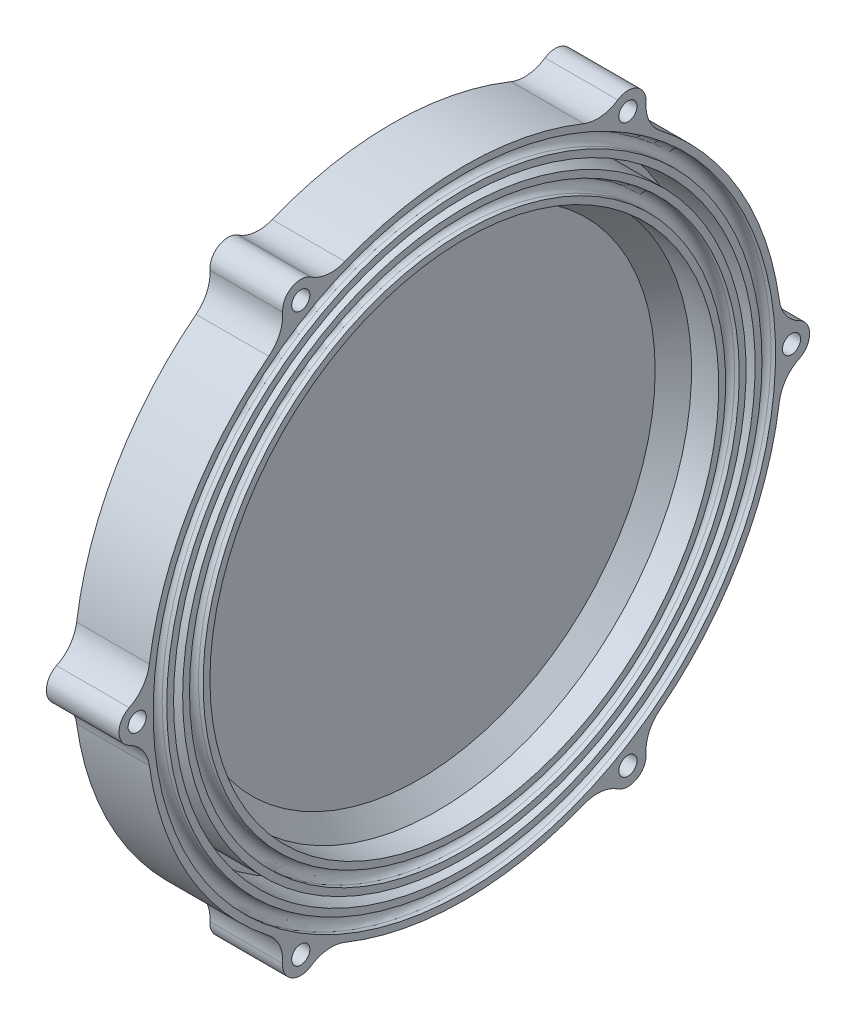
SolidWorks part; units mm, degrees
material "6061 Alloy"
ref_plane "Front Plane" through (0, 0, 0) normal (0, 0, 1) x (1, 0, 0)
ref_plane "Top Plane" through (0, 0, 0) normal (0, 1, 0) x (1, 0, 0)
ref_plane "Right Plane" through (0, 0, 0) normal (1, 0, 0) x (0, 0, -1)
sketch "Sketch1" plane through (0, 0, 0) normal (0, 0, 1) x (1, 0, 0)
  line L0 (0, 0) -> (144.1194, 0) construction
  line L1 (0, 111.125) -> (0, 0)
  line L9 (9.525, 82.55) -> (9.525, 0)
  line L10 (0, 0) -> (9.525, 0)
  line L11 (15.875, 88.9) -> (9.525, 82.55)
  line L12 (0, 111.125) -> (25.4, 111.125)
  line L13 (25.4, 111.125) -> (25.4, 101.6)
  line L18 (25.4, 88.9) -> (15.875, 88.9)
  line L19 (25.4, 101.6) -> (6.35, 101.6)
  line L20 (6.35, 101.6) -> (6.35, 98.425)
  line L21 (6.35, 98.425) -> (25.4, 98.425)
  line L22 (25.4, 98.425) -> (25.4, 88.9)
  dimension "D1" = 25.4
  dimension "D2" = 196.85
  dimension "D3" = 203.2
  dimension "D4" = 9.525
  dimension "D5" = 9.525
  dimension "D6" = 19.05
  dimension "D7" = 6.35
  dimension "D8" = 6.35
revolve "Revolve1" add sketch "Sketch1" angle 360 about L0
sketch "Sketch2" plane through (0, 0, 0) normal (-1, 0, 0) x (0, 0, 1)
  circle A0 centre (0, 50.8) radius 12.7
  circle A1 centre (0, 0) radius 82.55
  circle A2 centre (0, 0) radius 82.55
  circle A3 centre (0, 0) radius 12.7
  circle A4 centre (35.921, 35.921) radius 12.7
  circle A5 centre (50.8, 0) radius 12.7
  circle A6 centre (35.921, -35.921) radius 12.7
  circle A7 centre (0, -50.8) radius 12.7
  circle A8 centre (-35.921, -35.921) radius 12.7
  circle A9 centre (-50.8, 0) radius 12.7
  circle A10 centre (-35.921, 35.921) radius 12.7
  point P22 (0, 0)
  dimension "D2" = 25.4
  dimension "D3" = 50.8
  dimension "D1" = 0
  dimension "D4" = 8
extrude "Cut-Extrude1" [suppressed] cut sketch "Sketch2" against normal through all contours A9 | A10 | A0 | A4 | A5 | A6 | A7 | A8
sketch "Sketch3" plane through (25.4, 0, 0) normal (1, 0, 0) x (0, 0, -1)
  circle A0 centre (-114.3, 0) radius 4.7625 construction
  circle A1 centre (-114.3, 0) radius 6.35
  arc A2 (-117.0781, -5.71) -> (-110.0565, -15.3732) centre (-122.6344, -17.1301) cw
  circle A3 centre (0, 0) radius 111.125 construction
  arc A4 (-117.0781, 5.71) -> (-110.0565, 15.3732) centre (-122.6344, 17.1301) ccw
  circle A5 centre (0, 0) radius 114.3 construction
  circle A6 centre (0, 0) radius 111.125
  circle A7 centre (-114.3, 0) radius 3.175
  dimension "D1" = 9.525
  dimension "D2" = 12.7
  dimension "D3" = 228.6
  dimension "D4" = 12.7
  dimension "D5" = 6.35
extrude "Boss-Extrude1" add sketch "Sketch3" against normal up to surface (25.4 mm away) contours A4 A1 A2 | A1 A7 | A6 A1 | A1 A2 region at (25.4, 6.1835, 114.006) region at (25.4, 8.2808, 112.2187) region at (25.4, -8.2808, 112.2187) region at (25.4, 0, 109.7977) up to face at (0, 0, 111.125)
pattern_circular "CirPattern1" count 6 over 360 about axis through (0, 0, 0) along (-1, 0, 0) of "Boss-Extrude1"
sketch "Sketch4" plane through (25.4, 0, 0) normal (1, 0, 0) x (0, 0, -1)
  line L0 (0, 0) -> (-96.2371, 55.5625) construction
  line L1 (-96.2371, 55.5625) -> (-87.9882, 50.8)
  line L2 (-85.2386, 49.2125) -> (-76.9897, 44.45)
  circle A0 centre (0, 0) radius 98.425 construction
  arc A1 (-110.0565, -15.3732) -> (-68.3418, -87.6251) centre (0, 0) ccw construction
  arc A2 (-63.4841, -98.5376) -> (-68.3418, -87.6251) centre (-76.1523, -97.6394) ccw construction
  arc A3 (-63.4841, -98.5376) -> (-53.594, -104.2476) centre (-57.15, -98.9867) ccw construction
  arc A4 (-41.7147, -102.9983) -> (-53.594, -104.2476) centre (-46.4821, -114.7695) ccw construction
  arc A5 (-41.7147, -102.9983) -> (41.7147, -102.9983) centre (0, 0) ccw construction
  arc A6 (53.594, -104.2476) -> (41.7147, -102.9983) centre (46.4821, -114.7695) ccw construction
  arc A7 (53.594, -104.2476) -> (63.4841, -98.5376) centre (57.15, -98.9867) ccw construction
  arc A8 (68.3418, -87.6251) -> (63.4841, -98.5376) centre (76.1523, -97.6394) ccw construction
  arc A9 (68.3418, -87.6251) -> (110.0565, -15.3732) centre (0, 0) ccw construction
  arc A10 (117.0781, -5.71) -> (110.0565, -15.3732) centre (122.6344, -17.1301) ccw construction
  arc A11 (117.0781, -5.71) -> (117.0781, 5.71) centre (114.3, 0) ccw construction
  arc A12 (110.0565, 15.3732) -> (117.0781, 5.71) centre (122.6344, 17.1301) ccw construction
  arc A13 (110.0565, 15.3732) -> (68.3418, 87.6251) centre (0, 0) ccw construction
  arc A14 (63.4841, 98.5376) -> (68.3418, 87.6251) centre (76.1523, 97.6394) ccw construction
  arc A15 (63.4841, 98.5376) -> (53.594, 104.2476) centre (57.15, 98.9867) ccw construction
  arc A16 (41.7147, 102.9983) -> (53.594, 104.2476) centre (46.4821, 114.7695) ccw construction
  arc A17 (41.7147, 102.9983) -> (-41.7147, 102.9983) centre (0, 0) ccw construction
  arc A18 (-53.594, 104.2476) -> (-41.7147, 102.9983) centre (-46.4821, 114.7695) ccw construction
  arc A19 (-53.594, 104.2476) -> (-63.4841, 98.5376) centre (-57.15, 98.9867) ccw construction
  arc A20 (-68.3418, 87.6251) -> (-63.4841, 98.5376) centre (-76.1523, 97.6394) ccw construction
  arc A21 (-68.3418, 87.6251) -> (-110.0565, 15.3732) centre (0, 0) ccw construction
  arc A22 (-117.0781, 5.71) -> (-110.0565, 15.3732) centre (-122.6344, 17.1301) ccw construction
  arc A23 (-117.0781, 5.71) -> (-117.0781, -5.71) centre (-114.3, 0) ccw construction
  arc A24 (-110.0565, -15.3732) -> (-117.0781, -5.71) centre (-122.6344, -17.1301) ccw construction
  circle A25 centre (0, 0) radius 98.425 construction
  arc A26 (-110.0565, -15.3732) -> (-68.3418, -87.6251) centre (0, 0) ccw
  arc A27 (-63.4841, -98.5376) -> (-68.3418, -87.6251) centre (-76.1523, -97.6394) ccw
  arc A28 (-63.4841, -98.5376) -> (-53.594, -104.2476) centre (-57.15, -98.9867) ccw
  arc A29 (-41.7147, -102.9983) -> (-53.594, -104.2476) centre (-46.4821, -114.7695) ccw
  arc A30 (-41.7147, -102.9983) -> (41.7147, -102.9983) centre (0, 0) ccw
  arc A31 (53.594, -104.2476) -> (41.7147, -102.9983) centre (46.4821, -114.7695) ccw
  arc A32 (53.594, -104.2476) -> (63.4841, -98.5376) centre (57.15, -98.9867) ccw
  arc A33 (68.3418, -87.6251) -> (63.4841, -98.5376) centre (76.1523, -97.6394) ccw
  arc A34 (68.3418, -87.6251) -> (110.0565, -15.3732) centre (0, 0) ccw
  arc A35 (117.0781, -5.71) -> (110.0565, -15.3732) centre (122.6344, -17.1301) ccw
  arc A36 (117.0781, -5.71) -> (117.0781, 5.71) centre (114.3, 0) ccw
  arc A37 (110.0565, 15.3732) -> (117.0781, 5.71) centre (122.6344, 17.1301) ccw
  arc A38 (110.0565, 15.3732) -> (68.3418, 87.6251) centre (0, 0) ccw
  arc A39 (63.4841, 98.5376) -> (68.3418, 87.6251) centre (76.1523, 97.6394) ccw
  arc A40 (63.4841, 98.5376) -> (53.594, 104.2476) centre (57.15, 98.9867) ccw
  arc A41 (41.7147, 102.9983) -> (53.594, 104.2476) centre (46.4821, 114.7695) ccw
  arc A42 (41.7147, 102.9983) -> (-41.7147, 102.9983) centre (0, 0) ccw
  arc A43 (-53.594, 104.2476) -> (-41.7147, 102.9983) centre (-46.4821, 114.7695) ccw
  arc A44 (-53.594, 104.2476) -> (-63.4841, 98.5376) centre (-57.15, 98.9867) ccw
  arc A45 (-68.3418, 87.6251) -> (-63.4841, 98.5376) centre (-76.1523, 97.6394) ccw
  arc A46 (-68.3418, 87.6251) -> (-110.0565, 15.3732) centre (0, 0) ccw construction
  arc A47 (-117.0781, 5.71) -> (-110.0565, 15.3732) centre (-122.6344, 17.1301) ccw
  arc A48 (-117.0781, 5.71) -> (-117.0781, -5.71) centre (-114.3, 0) ccw
  arc A49 (-110.0565, -15.3732) -> (-117.0781, -5.71) centre (-122.6344, -17.1301) ccw
  circle A50 centre (0, 0) radius 88.9 construction
  circle A51 centre (0, 0) radius 101.6 construction
  circle A52 centre (0, 0) radius 88.9 construction
  circle A53 centre (0, 0) radius 101.6 construction
  circle A54 centre (0, 0) radius 106.3625
  circle A55 centre (0, 0) radius 93.6625
  point P27 (-87.9882, 50.8)
  point P33 (-96.2371, 55.5625)
  point P37 (-85.2386, 49.2125)
  point P39 (-76.9897, 44.45)
  point P51 (-92.1126, 53.1813)
  point P55 (-81.1141, 46.8313)
sketch "Sketch6" plane through (0, 0, 0) normal (0, 0, 1) x (1, 0, 0)
  line L1 (25.4, -106.3625) -> (25.4, 106.3625) construction
  line L2 (0, 0) -> (82.9529, 0) construction
  line L3 (23.8125, 103.9813) -> (36.1274, 103.9813) construction
  line L4 (23.8125, 91.2812) -> (38.8645, 91.2812) construction
  line L6 (23.8125, 93.6625) -> (25.4, 93.6625) construction
  line L7 (23.8125, 106.3625) -> (25.4, 106.3625) construction
  line L8 (25.4, -93.6625) -> (25.4, 93.6625) construction
  line L9 (23.8125, 108.7438) -> (26.1937, 108.7438)
  line L11 (23.8125, 103.9813) -> (26.1937, 103.9813)
  line L12 (26.1937, 108.7438) -> (26.1937, 103.9813)
  line L13 (22.1287, 108.0463) -> (26.1937, 103.9813) construction
  line L14 (22.1287, 104.6787) -> (26.1937, 108.7438) construction
  line L15 (23.8125, 91.2812) -> (26.1937, 91.2812)
  line L17 (23.8125, 96.0437) -> (26.1937, 96.0437)
  line L18 (26.1937, 91.2812) -> (26.1937, 96.0437)
  line L19 (22.1287, 91.9787) -> (26.1937, 96.0437) construction
  line L20 (22.1287, 95.3463) -> (26.1937, 91.2812) construction
  arc A0 (23.8125, 108.7438) -> (23.8125, 103.9813) centre (23.8125, 106.3625) ccw
  arc A1 (23.8125, 96.0437) -> (23.8125, 91.2812) centre (23.8125, 93.6625) ccw
  point P27 (25.4, 93.6625)
  point P30 (25.4, 106.3625)
  dimension "D3" = 4.7625
  dimension "D1" = 91.2812
  dimension "D4" = 1.5875
sweep "Cut-Sweep1" cut profiles "Sketch6" path "Sketch4"
equation "\"Tube OD\"= 8"
equation "\"Tube Wall\"= .25"
equation "\"Tube ID\"= \"Tube OD\" - \"Tube Wall\""
equation "\"Back Thickness\"= 1"
equation "\"Total Thickness\"=1"
equation "\"D1@Sketch1\"=\"Total Thickness\""
equation "\"D2@Sketch1\"=\"Tube ID\""
equation "\"D3@Sketch1\"=\"Tube OD\""
equation "\"Recess Distance\"=0.75"
equation "\"D6@Sketch1\"=\"Recess Distance\""
equation "\"Mouting Flange Diam\"= 9"
equation "\"D3@Sketch3\"=\"Mouting Flange Diam\""
